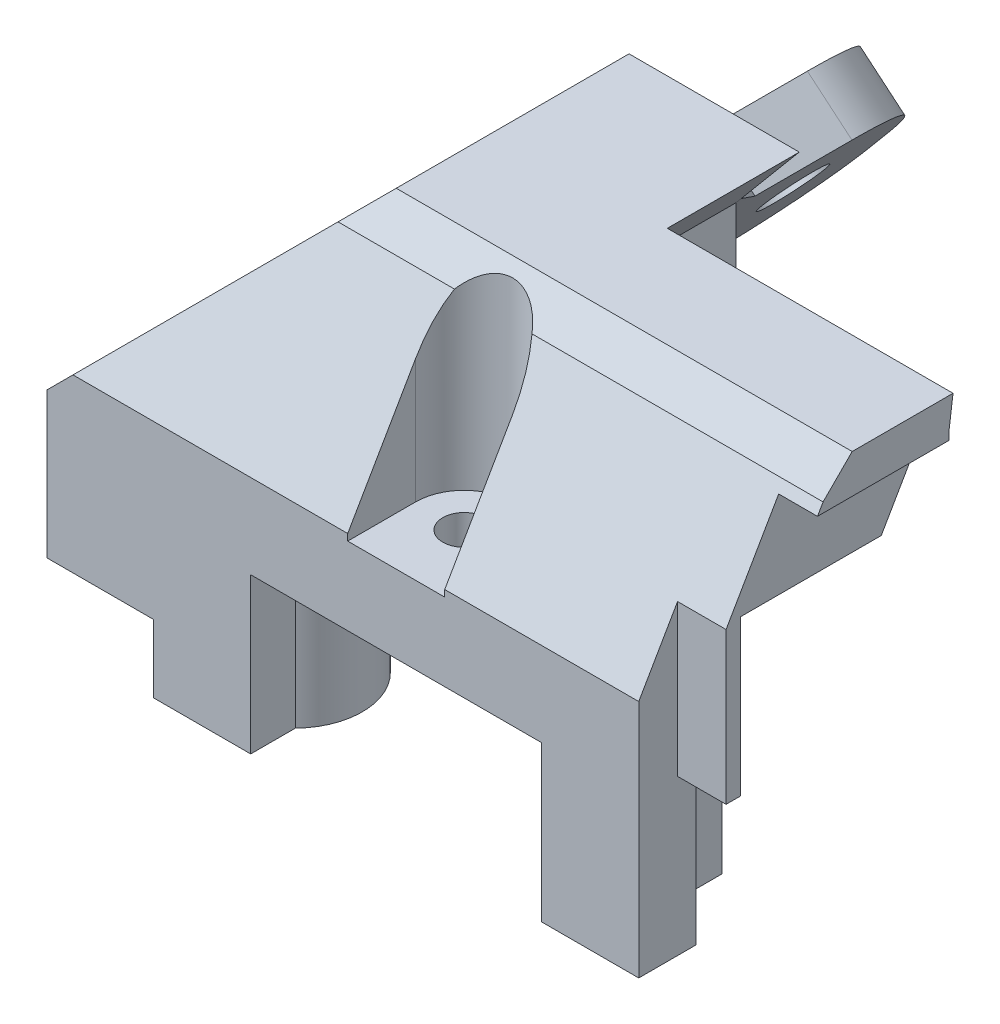
SolidWorks part; units mm, degrees
ref_plane "前视基准面" through (0, 0, 0) normal (0, 0, 1) x (1, 0, 0)
ref_plane "上视基准面" through (0, 0, 0) normal (0, 1, 0) x (1, 0, 0)
ref_plane "右视基准面" through (0, 0, 0) normal (1, 0, 0) x (0, 0, -1)
sketch "草图1" plane through (0, 0, 0) normal (0, 1, 0) x (1, 0, 0)
  line L1 (-18, 8) -> (10, 8)
  line L2 (-18, 8) -> (-18, -3.5)
  line L3 (-18, -3.5) -> (10, -3.5)
  line L4 (10, 8) -> (10, -3.5)
  circle A0 centre (0, 0) radius 1.1
  dimension "D1" = 2.2
  dimension "D2" = 3.5
  dimension "D3" = 10
  dimension "D4" = 18
  dimension "D5" = 8
extrude "凸台-拉伸1" add sketch "草图1" along normal blind 3
sketch "草图2" plane through (0, 0, 0) normal (0, -1, 0) x (1, 0, 0)
  line L0 (10, 2.25) -> (10, -4.75)
  circle A0 centre (-10, -1.25) radius 3.5
  arc A1 (10, 2.25) -> (10, -4.75) centre (10, -1.25) ccw
  circle A2 centre (0, 0) radius 1.1 construction
  dimension "D3" = 7
  dimension "D4" = 20
  dimension "D1" = 1.25
  dimension "D2" = 10
extrude "凸台-拉伸2" add sketch "草图2" along normal blind 8
sketch "草图3" plane through (0, 0, 0) normal (0, -1, 0) x (1, 0, 0)
  line L0 (-15.5, -8) -> (-15.5, -4.05)
  line L1 (-15.5, -4.05) -> (10, -4.05)
  line L2 (10, -4.05) -> (10, -8)
  line L3 (10, -8) -> (-18, -8) construction
  line L4 (-15.5, -8) -> (10, -8)
  line L5 (10, -4.75) -> (10, 2.25) construction
  circle A2 centre (-10, -1.25) radius 3.5 construction
  circle A3 centre (-10, -1.25) radius 3.5 construction
  dimension "D2" = 5.5
  dimension "D4" = 2.8
extrude "切除-拉伸1" cut sketch "草图3" against normal through all and the other way through all
sketch "草图4" plane through (10, 0, 0) normal (1, 0, 0) x (0, 0, -1)
  line L0 (0, 3) -> (0, -8)
  line L6 (-2.25, -8) -> (4.05, -8)
  line L7 (4.05, -8) -> (4.05, 3)
  line L8 (4.05, 3) -> (-3.5, 3)
  line L9 (-3.5, 3) -> (-3.5, 0)
  line L10 (-3.5, 0) -> (-2.25, 0)
  line L11 (-2.25, 0) -> (-2.25, -8)
  line L12 (-2.25, -8) -> (0, -8)
  line L14 (0, 3) -> (-3.5, 3)
  line L15 (-3.5, 3) -> (-3.5, 0)
  line L16 (-3.5, 0) -> (-2.25, 0)
  line L17 (-2.25, 0) -> (-2.25, -8)
  dimension "D2" = 3.5
  dimension "D1" = 0
extrude "凸台-拉伸3" add sketch "草图4" along normal blind 3
sketch "草图5" plane through (13, 0, 0) normal (1, 0, 0) x (0, 0, -1)
  line L1 (-3.5, 0) -> (0, 0)
  line L2 (-3.5, 0) -> (-3.5, 3)
  line L3 (-3.5, 3) -> (0, 3)
  line L4 (0, 0) -> (0, 3)
extrude "凸台-拉伸4" add sketch "草图5" along normal blind 2
sketch "草图6" plane through (0, 3, 0) normal (0, 1, 0) x (1, 0, 0)
  line L0 (-2.5, 0) -> (-2.5, -3.5)
  line L1 (2.5, 0) -> (2.5, -3.5)
  line L2 (2.5, -3.5) -> (15, -3.5)
  line L8 (-15.5, 4.05) -> (-15.5, 8)
  line L9 (-15.5, 8) -> (-18, 8)
  line L10 (-18, 8) -> (-18, -3.5)
  line L11 (-18, -3.5) -> (15, -3.5)
  line L12 (15, -3.5) -> (15, 0)
  line L13 (15, 0) -> (10, 0)
  line L14 (10, 0) -> (10, 4.05)
  line L15 (10, 4.05) -> (-15.5, 4.05)
  line L16 (-15.5, 4.05) -> (-15.5, 8)
  line L17 (-15.5, 8) -> (-18, 8)
  line L18 (-18, 8) -> (-18, -3.5)
  line L19 (-18, -3.5) -> (-2.5, -3.5)
  line L20 (15, -3.5) -> (15, 0)
  line L21 (15, 0) -> (10, 0)
  line L22 (10, 0) -> (10, 4.05)
  line L23 (10, 4.05) -> (-15.5, 4.05)
  arc A0 (2.5, 0) -> (-2.5, 0) centre (0, 0) ccw
  dimension "D1" = 5
  dimension "D2" = 0
extrude "凸台-拉伸5" add sketch "草图6" along normal blind 5
sketch "草图7" plane through (0, 8, 0) normal (0, 1, 0) x (1, 0, 0)
  line L0 (15, 0) -> (15, 8)
  line L1 (15, 8) -> (-18, 8)
  line L8 (10, 4.05) -> (-15.5, 4.05)
  line L9 (-15.5, 4.05) -> (-15.5, 8)
  line L10 (-15.5, 8) -> (-18, 8)
  line L11 (-18, 8) -> (-18, -3.5)
  line L12 (-18, -3.5) -> (-2.5, -3.5)
  line L13 (15, -3.5) -> (15, 0)
  line L14 (15, 0) -> (10, 0)
  line L15 (10, 0) -> (10, 4.05)
  line L19 (-18, 8) -> (-18, -3.5)
  line L20 (-18, -3.5) -> (-2.5, -3.5)
  line L21 (15, -3.5) -> (15, 0)
  line L30 (-2.5, -3.5) -> (-2.5, 0)
  line L31 (-2.5, -3.5) -> (-2.5, 0)
  line L32 (2.5, 0) -> (2.5, -3.5)
  line L33 (2.5, 0) -> (2.5, -3.5)
  line L34 (2.5, -3.5) -> (15, -3.5)
  line L35 (2.5, -3.5) -> (15, -3.5)
  circle A0 centre (0, 0) radius 2.5 construction
  arc A1 (2.5, 0) -> (-2.5, 0) centre (0, 0) ccw
  arc A3 (2.5, 0) -> (-2.5, 0) centre (0, 0) ccw
  arc A4 (2.5, 0) -> (-2.5, 0) centre (0, 0) ccw
  line M10 (10, 4.05) -> (-15.5, 4.05)
  line M11 (-15.5, 4.05) -> (-15.5, 8)
  line M12 (-15.5, 8) -> (-18, 8)
  line M13 (-18, 8) -> (-18, -3.5)
  line M14 (-18, -3.5) -> (-2.5, -3.5)
  line M15 (15, -3.5) -> (15, 0)
  line M16 (15, 0) -> (10, 0)
  line M17 (10, 0) -> (10, 4.05)
  arc M18 (-2.5, 0) -> (2.5, 0) centre (0, 0) cw
  line M22 (-2.5, -3.5) -> (-2.5, 0)
  line M23 (2.5, 0) -> (2.5, -3.5)
  line M24 (2.5, -3.5) -> (15, -3.5)
  dimension "D1" = 0
extrude "凸台-拉伸6" add sketch "草图7" along normal blind 5 contours M17 M10 M11 M12 M13 M14 M22 M18 M23 M24 M15 M16 | L0 L1 M11 M10 M17 M16 region at (1.5847, 8, -5.4494) region at (-3.7466, 8, -0.507)
sketch "草图8" plane through (0, 8, 0) normal (0, -1, 0) x (1, 0, 0)
  line L1 (10, -4.05) -> (-15.5, -4.05)
  line L2 (10, -4.05) -> (10, -8)
  line L3 (10, -8) -> (-15.5, -8)
  line L4 (-15.5, -4.05) -> (-15.5, -8)
extrude "凸台-拉伸7" add sketch "草图8" along normal blind 3
sketch "草图9" plane through (0, 0, 0) normal (0, -1, 0) x (1, 0, 0)
  line L0 (-12.1, -4.05) -> (-15.5, -4.05)
  line L1 (-18, -8) -> (-18, 3.5) construction
  line L2 (-18, -4.05) -> (-18, 3.5)
  line L3 (-18, 3.5) -> (-7.5, 3.5)
  line L4 (-18, 3.5) -> (15, 3.5) construction
  line L5 (-7.5, 3.5) -> (-7.5, 1.1995)
  line L8 (-15.5, -4.05) -> (-15.5, -8)
  line L9 (-15.5, -8) -> (-18, -8)
  line L10 (-18, -4.05) -> (-18, -8)
  arc A0 (-7.9, -4.05) -> (-12.1, -4.05) centre (-10, -1.25) ccw construction
  arc A1 (-7.5, 1.1995) -> (-12.1, -4.05) centre (-10, -1.25) ccw
  arc A2 (-7.9, -4.05) -> (-12.1, -4.05) centre (-10, -1.25) ccw construction
  dimension "D1" = 2.5
extrude "凸台-拉伸8" add sketch "草图9" along normal blind 4.5
sketch "草图10" plane through (0, 0, -8) normal (0, 0, -1) x (-1, 0, 0)
  line L1 (15.5, -4.5) -> (18, -4.5)
  line L2 (15.5, -4.5) -> (15.5, 13)
  line L3 (15.5, 13) -> (18, 13)
  line L4 (18, -4.5) -> (18, 13)
extrude "凸台-拉伸9" add sketch "草图10" along normal blind 7
sketch "草图11" plane through (0, 5, 0) normal (0, -1, 0) x (1, 0, 0)
  line L0 (-15.5, -15) -> (-15.5, -4.05) construction
  line L1 (10, -8) -> (-15.5, -8)
  line L2 (10, -8) -> (10, -6.5)
  line L3 (10, -6.5) -> (-15.5, -6.5)
  line L4 (-15.5, -8) -> (-15.5, -6.5)
  dimension "D1" = 1.5
extrude "切除-拉伸2" cut sketch "草图11" against normal up to surface (3 mm away) up to face at (12.5, 8, -4)
chamfer "倒角1" distance 1.5 angle 60 1 edges at (-0.25, 8, -8) first distance on face at (3.1667, 8, -4.8333)
sketch "草图12" plane through (0, -4.5, 0) normal (0, -1, 0) x (1, 0, 0)
  line L0 (-10, -1.25) -> (-10, 3.5) construction
  line L1 (-7.5, 3.5) -> (-18, 3.5) construction
  line L2 (-12.5, 3.5) -> (-12.5, 1.1995)
  line L3 (-12.5, 3.5) -> (-7.5, 3.5)
  line L4 (-7.5, 3.5) -> (-7.5, 1.1995)
  line L5 (0, 0) -> (0, 3.5) construction
  line L6 (-7.5, 3.5) -> (15, 3.5) construction
  line L7 (7.5, 3.5) -> (7.5, 1.1995)
  line L8 (12.5, 3.5) -> (7.5, 3.5)
  line L10 (13, 2.25) -> (13, 3.5)
  line L11 (13, 3.5) -> (12.5, 3.5)
  line L12 (13, 2.25) -> (12.5, 2.25)
  line L13 (13, 2.25) -> (10, 2.25) construction
  line L14 (12.5, 2.25) -> (10, 2.25)
  arc A0 (-7.5, 1.1995) -> (-12.1, -4.05) centre (-10, -1.25) ccw construction
  arc A1 (-7.9, -4.05) -> (-12.1, -4.05) centre (-10, -1.25) ccw construction
  arc A2 (-7.5, 1.1995) -> (-12.5, 1.1995) centre (-10, -1.25) ccw
  arc A3 (7.5, 1.1995) -> (10, 2.25) centre (10, -1.25) cw
extrude "凸台-拉伸10" add sketch "草图12" along normal up to surface and the other way up to surface up to face at (-10, -8, -0.9) other way up to face at (0, 0, 1.1)
sketch "草图13" plane through (13, 0, 0) normal (1, 0, 0) x (0, 0, -1)
  line L4 (0, 0) -> (-3.5, 0)
  line L5 (-3.5, 0) -> (-3.5, -8)
  line L6 (-3.5, -8) -> (0, -8)
  line L7 (0, -8) -> (0, 0)
  line L8 (0, 0) -> (-3.5, 0)
  line L9 (-3.5, 0) -> (-3.5, -8)
  line L10 (-3.5, -8) -> (0, -8)
  line L11 (0, -8) -> (0, 0)
  dimension "D1" = 0
extrude "切除-拉伸3" cut sketch "草图13" against normal blind 0.3
chamfer "倒角2" distance 0.75 angle 45 4 edges at (10, -1.5, -4.05) (10, 6.5, -6.5) (12.7, -4, 0) (15, 4, 0)
sketch "草图14" plane through (0, -4.5, 0) normal (0, -1, 0) x (1, 0, 0)
  line L1 (12.5, 3.5) -> (15, 3.5)
  line L2 (12.5, 3.5) -> (12.5, 1.5)
  line L3 (12.5, 1.5) -> (15, 1.5)
  line L4 (15, 3.5) -> (15, 1.5)
  dimension "D1" = 2.5
  dimension "D2" = 2
extrude "切除-拉伸4" cut sketch "草图14" against normal through all and the other way up to next
sketch "草图15" plane through (0, 0, 1.5) normal (0, 0, 1) x (1, 0, 0)
  line L1 (15, 0) -> (12.5, 0)
  line L2 (15, 0) -> (15, -8)
  line L3 (15, -8) -> (12.5, -8)
  line L4 (12.5, 0) -> (12.5, -8)
extrude "切除-拉伸5" cut sketch "草图15" against normal up to next
sketch "草图16" plane through (0, 3, 0) normal (0, 1, 0) x (1, 0, 0)
  line L3 (2.5, -3.5) -> (2.5, 0)
  line L4 (-2.5, 0) -> (-2.5, -3.5)
  line L5 (-2.5, -3.5) -> (2.5, -3.5)
  line L6 (2.5, -3.5) -> (2.5, 0)
  line L7 (-2.5, 0) -> (-2.5, -3.5)
  line L8 (-2.5, -3.5) -> (2.5, -3.5)
  circle A0 centre (0, 0) radius 1.1 construction
  arc A1 (2.5, 0) -> (-2.5, 0) centre (0, 0) ccw
  arc A2 (2.5, 0) -> (-2.5, 0) centre (0, 0) ccw
  circle A3 centre (0, 0) radius 1.1
  dimension "D1" = 0
extrude "凸台-拉伸11" add sketch "草图16" along normal offset from surface (1 mm away) 4 up to face at (0, 0, 1.1)
sketch "草图18" plane through (0, 0, -6.5) normal (0, 0, -1) x (-1, 0, 0)
  line L0 (15.5, 13) -> (15.5, -4.5) construction
  line L1 (15.5, 5) -> (8.5, 5)
  line L2 (15.5, 5) -> (15.5, 13)
  line L3 (15.5, 13) -> (1, 13)
  line L5 (15.5, 5) -> (15.5, -4.5) construction
  line L6 (-15, 13) -> (15.5, 13) construction
  line L7 (-9.25, 5) -> (15.5, 5) construction
  line L8 (-9.25, 5) -> (15.5, 5) construction
  line L9 (1, 10.5981) -> (8.5, 10.5981)
  line L10 (-15, 10.5981) -> (15.5, 10.5981) construction
  line L11 (8.5, 10.5981) -> (8.5, 5)
  line L12 (1, 10.5981) -> (-1.0155, 13)
  line L13 (-1.0155, 13) -> (1, 13)
  dimension "D1" = 14.5
  dimension "D2" = 7
  dimension "D3" = 130
extrude "凸台-拉伸12" add sketch "草图18" along normal up to surface (8.5 mm away) up to face at (-16.75, 4.25, -15)
sketch "草图19" plane through (15, 0, 0) normal (1, 0, 0) x (0, 0, -1)
  line L0 (8, 13) -> (8, 10.5981) construction
  line L1 (-1.5, 14.5) -> (8, 14.5)
  line L2 (-1.5, 14.5) -> (-1.5, 12.5)
  line L3 (-1.5, 12.5) -> (8, 12.5)
  line L4 (8, 14.5) -> (8, 12.5)
  line L5 (-1.5, 13) -> (8, 13) construction
  line L6 (-1.5, 13) -> (-1.5, 0) construction
  dimension "D1" = 2
  dimension "D2" = 0.5
sketch "草图20" plane through (0, 10.5981, 0) normal (0, -1, 0) x (1, 0, 0)
  line L0 (-1, -15) -> (-1, -8) construction
  line L1 (-8.5, -15) -> (-1, -15)
  line L2 (-8.5, -15) -> (-8.5, -12)
  line L3 (-8.5, -12) -> (-1, -12)
  line L4 (-1, -15) -> (-1, -12)
  dimension "D1" = 3
extrude "凸台-拉伸14" add sketch "草图20" along normal up to surface (5.5981 mm away) up to face at (-1.1875, 5, -7.5187)
sketch "草图21" plane through (0, 0, -12) normal (0, 0, 1) x (1, 0, 0)
  line L0 (-1, 5) -> (-3.9368, 1.5)
  line L1 (-3.9368, 1.5) -> (-8.5, 1.5)
  line L2 (-15.5, 5) -> (-15.5, -4.5) construction
  line L3 (-15.5, 1.5) -> (-15.5, 5)
  line L4 (-15.5, 5) -> (-1, 5)
  line L5 (-8.5, 1.5) -> (-10.388, -0.75)
  line L6 (-10.388, -0.75) -> (-15.5, -0.75)
  line L7 (-15.5, 5) -> (-15.5, -4.5) construction
  line L8 (-15.5, -0.75) -> (-15.5, 1.5)
  dimension "D1" = 50
  dimension "D2" = 3.5
  dimension "D3" = 7
  dimension "D4" = 2.25
extrude "凸台-拉伸15" add sketch "草图21" against normal up to surface (3 mm away) up to face at (-9.7121, 5.3712, -15)
sketch "草图23" plane through (0, 0, -15) normal (0, 0, -1) x (-1, 0, 0)
  line L0 (8.5, 1.5) -> (15.5, 1.5)
  line L1 (15.5, 1.5) -> (15.5, -0.75)
  line L2 (15.5, -0.75) -> (10.388, -0.75)
  line L3 (10.388, -0.75) -> (8.5, 1.5)
extrude "切除-拉伸6" cut sketch "草图23" against normal blind 2
sketch "草图24" plane through (0, -4.5, 0) normal (0, -1, 0) x (1, 0, 0)
  line L0 (-15.5, -4.05) -> (-15.5, -12) construction
  line L1 (-18, -15) -> (-15.5, -15)
  line L2 (-18, -15) -> (-18, -4.55)
  line L3 (-18, -4.55) -> (-15.5, -4.55)
  line L4 (-15.5, -15) -> (-15.5, -4.55)
  line L5 (-15.5, -15) -> (-15.5, -4.05) construction
  line L6 (-15.5, -4.05) -> (-12.1, -4.05) construction
  dimension "D1" = 0.5
extrude "凸台-拉伸16" add sketch "草图24" along normal blind 2
sketch "草图25" plane through (0, 0, -13) normal (0, 0, -1) x (-1, 0, 0)
  line L1 (15.5, 1.5) -> (2.2586, 1.5)
  line L2 (15.5, 1.5) -> (15.5, 3.5)
  line L3 (15.5, 3.5) -> (2.2586, 3.5)
  line L4 (2.2586, 1.5) -> (2.2586, 3.5)
  line L5 (1, 5) -> (3.9368, 1.5) construction
  dimension "D1" = 2
extrude "切除-拉伸7" cut sketch "草图25" along normal up to next
chamfer "倒角3" distance 1.5 angle 45 1 edges at (-4.75, 10.5981, -12)
chamfer "倒角5" distance 5 angle 60 2 edges at (-10.25, 13, 3.5) (7.5, 13, 3.5) first distance on face at (1.7526, 13, -2.625) first distance on face at (-2.5714, 1.3571, 3.5)
chamfer "倒角6" distance 10 angle 45 1 edges at (-18, 13, -8.25)
chamfer "倒角7" distance 2 angle 45 1 edges at (-15.5, 3.5, -14)
chamfer "倒角8" distance 2 angle 45 2 edges at (-15.5, 5, -8.025) (-8.5, 10.5981, -9.25)
sketch "草图28" plane through (0, 13, 0) normal (0, 1, 0) x (1, 0, 0)
  line L7 (1.0155, 15) -> (-8, 15)
  line L8 (-8, 15) -> (-8, 1.5)
  line L9 (-8, 1.5) -> (-2, 1.5)
  line L10 (2, 1.5) -> (15, 1.5)
  line L11 (15, 1.5) -> (15, 8)
  line L12 (15, 8) -> (1.0155, 8)
  line L13 (1.0155, 8) -> (1.0155, 15)
  line L14 (1.0155, 15) -> (-8, 15)
  line L15 (-8, 15) -> (-8, 1.5)
  line L16 (-8, 1.5) -> (-2, 1.5)
  line L17 (2, 1.5) -> (15, 1.5)
  line L18 (15, 1.5) -> (15, 8)
  line L19 (15, 8) -> (1.0155, 8)
  line L20 (1.0155, 8) -> (1.0155, 15)
  arc A1 (2, 1.5) -> (-2, 1.5) centre (0, 0) ccw
  arc A2 (2, 1.5) -> (-2, 1.5) centre (0, 0) ccw
  dimension "D1" = 0
extrude "凸台-拉伸17" add sketch "草图28" along normal blind 1.5
sketch "草图29" plane through (15, 0, 0) normal (1, 0, 0) x (0, 0, -1)
  line L0 (1.5, 14.5) -> (1.5, 13)
  line L1 (1.5, 13) -> (1.2113, 12.5)
  line L2 (-1.5, 12.5) -> (8, 12.5) construction
  line L3 (1.5, 13) -> (-1.5, 7.8038) construction
  line L4 (1.2113, 12.5) -> (8, 12.5)
  line L5 (8, 12.5) -> (8, 14.5)
  line L6 (8, 14.5) -> (1.5, 14.5)
sketch "草图34" plane through (0, 0, -13) normal (0, 0, -1) x (-1, 0, 0)
  line L0 (2.2586, 3.5) -> (3.0977, 2.5)
  line L1 (2.2586, 3.5) -> (3.9368, 1.5) construction
  line L2 (3.0977, 2.5) -> (14.5, 2.5)
  line L3 (13.5, 3.5) -> (15.5, 1.5) construction
  line L4 (14.5, 2.5) -> (13.5, 3.5)
  line L5 (13.5, 3.5) -> (2.2586, 3.5)
  dimension "D1" = 1
extrude "凸台-拉伸21" add sketch "草图34" along normal up to surface (2 mm away) up to face at (-8.2273, 5.7582, -15)
extrude "凸台-拉伸18" add sketch "草图29" along normal blind 2
chamfer "倒角9" distance 1.5 angle 45 2 edges at (-5, 14.5, -1.5) (-8, 14.5, -8.25)
sketch "草图30" plane through (1.0155, 0, 0) normal (1, 0, 0) x (0, 0, -1)
  line L0 (8, 13) -> (8.1975, 14.5)
  line L1 (8, 14.5) -> (15, 14.5) construction
  line L2 (8.1975, 14.5) -> (8, 14.5)
  line L3 (8, 14.5) -> (8, 13)
  dimension "D1" = 7.5
extrude "凸台-拉伸19" add sketch "草图30" along normal up to surface (15.9845 mm away) up to face at (17, 13.4, -4.3423)
sketch "草图32" plane through (0, 0, -15) normal (0, 0, -1) x (-1, 0, 0)
  line L0 (-1.0155, 13) -> (-2.2741, 14.5)
  line L1 (-17, 14.5) -> (-1.0155, 14.5) construction
  line L2 (-2.2741, 14.5) -> (-1.0155, 14.5)
  line L3 (-1.0155, 14.5) -> (-1.0155, 13)
  line L4 (1, 10.5981) -> (-1.0155, 13) construction
extrude "凸台-拉伸20" add sketch "草图32" against normal up to surface (6.8025 mm away) up to face at (9.0077, 13.75, -8.0987)
sketch "草图33" plane through (0, 0, -15) normal (0, 0, -1) x (-1, 0, 0)
  line L0 (1, 5) -> (1, 5.7779)
  line L1 (1, 5) -> (1, 10.5981) construction
  line L2 (1, 5.7779) -> (4.5896, 1.5)
  line L3 (3.9368, 1.5) -> (8.5, 1.5) construction
  line L4 (4.5896, 1.5) -> (3.9368, 1.5)
  line L5 (3.9368, 1.5) -> (1, 5)
  dimension "D1" = 0.5
extrude "切除-拉伸8" cut sketch "草图33" against normal up to surface (3 mm away) up to face at (-8.575, 4.2086, -12)
sketch "草图35" plane through (0, 0, -15) normal (0, 0, -1) x (-1, 0, 0)
  line L0 (2.01, 9.3944) -> (7.7951, 2.5)
  line L2 (-1.0155, 13) -> (1, 10.5981) construction
  line L3 (7.7951, 2.5) -> (11.7113, 2.5)
  line L5 (11.7113, 2.5) -> (4.3081, 11.3228)
  line L9 (3.7505, 2.5) -> (14.5, 2.5) construction
  line L10 (2.01, 9.3944) -> (4.3081, 11.3228)
  dimension "D1" = 3
  dimension "D2" = 9
extrude "凸台-拉伸22" add sketch "草图35" along normal blind 12
sketch "草图36" plane through (-8.1035, 6.7996, 0) normal (-0.766, 0.6428, 0) x (0, 0, 1)
  line L0 (-27, -5.6128) -> (-27, 5.9045) construction
  line L1 (-27, 5.9045) -> (-15, 5.9045) construction
  circle A0 centre (-22.127, 0.9745) radius 1.6
  dimension "D1" = 3.2
  dimension "D3" = 4.93
  dimension "D2" = 4.873
extrude "切除-拉伸9" cut sketch "草图36" against normal up to surface (3 mm away) up to face at (-4.9025, 5.9472, -21)
sketch "草图37" plane through (0, 0, -27) normal (0, 0, -1) x (-1, 0, 0)
  line L0 (11.7113, 2.5) -> (7.7951, 2.5)
  line L1 (7.7951, 2.5) -> (9.4132, 0.5716)
  line L2 (9.4132, 0.5716) -> (11.7113, 2.5)
  line L3 (2.01, 9.3944) -> (7.7951, 2.5) construction
extrude "凸台-拉伸23" add sketch "草图37" against normal blind 10
fillet "圆角1" radius 5 2 edges at (-3.1591, 10.3586, -27) (-10.5622, 1.5358, -27)
chamfer "倒角10" distance 2 angle 45 2 edges at (-3.1591, 10.3586, -15) (-8.0097, 6.9114, -15)
